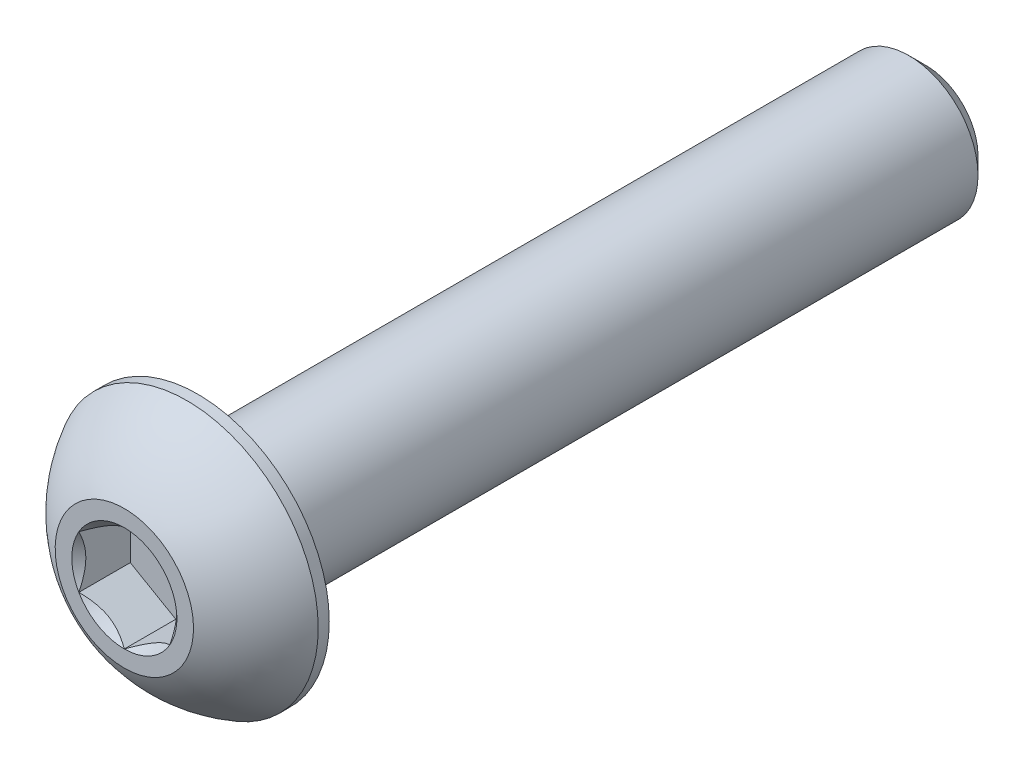
SolidWorks part; units mm, degrees
material "Alloy Steel"
ref_plane "Front" through (0, 0, 0) normal (0, 0, 1) x (1, 0, 0)
ref_plane "Top" through (0, 0, 0) normal (0, 1, 0) x (1, 0, 0)
ref_plane "Right" through (0, 0, 0) normal (1, 0, 0) x (0, 0, -1)
sketch "Sketch1" plane through (0, 0, 0) normal (1, 0, 0) x (0, 0, -1)
  line L2 (2.5654, 2.413) -> (27.9654, 2.413)
  line L3 (27.9654, 2.413) -> (27.9654, 0)
  line L4 (27.9654, 0) -> (2.5654, 0)
  line L6 (2.1806, 4.5847) -> (2.5654, 4.5847) construction
  line L7 (27.9654, 2.413) -> (27.9654, -2.413) construction
  line L8 (0, 0) -> (2.5654, 0) construction
  line L9 (2.5654, 4.5847) -> (2.5654, -4.5847) construction
  line L11 (2.5654, 2.413) -> (2.5654, 0)
  line L13 (0, 1.5875) -> (0, -1.5875) construction
  line L14 (0, 1.5875) -> (0, 2.413) construction
  arc A3 (0, 2.413) -> (2.1806, 4.5847) centre (4.5749, 0) cw construction
  dimension "D1" = 0.3848
revolve "Revolve1" add sketch "Sketch1" angle 360 mid plane about L4
sketch "Sketch3" plane through (0, 0, -27.9654) normal (0, 0, -1) x (-1, 0, 0)
  circle A0 centre (0, 0) radius 2.413
curve "Helix/Spiral1" pitch 0.7937 height 26.1937 turns 33
sketch "Sketch2" plane through (0, 0, 0) normal (1, 0, 0) x (0, 0, -1)
  line L0 (27.9654, 2.413) -> (28.6599, 2.413)
  line L1 (28.6599, 2.413) -> (28.3623, 1.8974)
  line L2 (28.3623, 1.8974) -> (28.2631, 1.8974)
  line L3 (28.2631, 1.8974) -> (27.9654, 2.413)
  line L4 (28.1142, 2.1552) -> (28.5111, 2.1552) construction
  dimension "D1" = 60
  dimension "D2" = 0.0992
  dimension "D3" = 0.3969
chamfer "Chamfer1" distance 0.5953 angle 45 1 edges at (0, 2.413, -27.9654)
sweep "Cut-Sweep1" [suppressed] cut profiles "Sketch2" path "Helix/Spiral1"
sketch "Sketch7" plane through (0, 0, 0) normal (1, 0, 0) x (0, 0, -1)
  line L6 (2.1806, 4.5847) -> (2.5654, 4.5847) construction
  line L8 (0, 0) -> (2.5654, 0) construction
  line L11 (2.5654, 4.5847) -> (2.5654, -4.5847) construction
  line L12 (2.1806, 4.5847) -> (2.5654, 4.5847)
  line L13 (0, 0) -> (2.5654, 0)
  line L14 (0, 1.5875) -> (0, -1.5875) construction
  line L15 (2.5654, 4.5847) -> (2.5654, 0)
  line L16 (0, 2.413) -> (0, 0)
  arc A2 (2.1806, 4.5847) -> (0, 2.413) centre (4.5749, 0) ccw construction
  arc A3 (2.1806, 4.5847) -> (0, 2.413) centre (4.5749, 0) ccw
revolve "Revolve2" add sketch "Sketch7" angle 360 mid plane about L13
sketch "Sketch5" plane through (0, 0, 0) normal (0, 0, 1) x (1, 0, 0)
  line L1 (1.5875, -0.9165) -> (1.5875, 0.9165)
  line L2 (1.5875, 0.9165) -> (0, 1.8331)
  line L3 (0, 1.8331) -> (-1.5875, 0.9165)
  line L4 (-1.5875, 0.9165) -> (-1.5875, -0.9165)
  line L5 (-1.5875, -0.9165) -> (0, -1.8331)
  line L6 (0, -1.8331) -> (1.5875, -0.9165)
  circle A0 centre (0, 0) radius 1.5875 construction
extrude "Cut-Extrude2" cut sketch "Sketch5" against normal blind 1.7958
sketch "Sketch6" plane through (0, 0, 0) normal (0, 0, 1) x (1, 0, 0)
  circle A0 centre (0, 0) radius 1.8331
extrude "Cut-Extrude3" cut sketch "Sketch6" against normal blind 1.7958 draft 45
sketch "Sketch9" [suppressed] plane through (0, 0, -2.2098) normal (0, 0, 1) x (1, 0, 0)
  circle A2 centre (0, 0) radius 2.0828
extrude "Boss-Extrude2" [suppressed] add sketch "Sketch9" against normal offset from surface (3.175 mm away) 22.225 up to face at (0, 1.8177, -27.9654)
sketch "Sketch10" plane through (0, 0, 0) normal (1, 0, 0) x (0, 0, -1)
  line L0 (27.9654, 2.413) -> (27.9654, -2.413) construction
  point P0 (26.7748, -2.413)
  dimension "D1" = 1.1906
equation "\"D3@Helix/Spiral1\" = \"Lg@Sketch1\" + \"D4@Helix/Spiral1\""
equation "\"D2@Sketch2\" = \"D4@Helix/Spiral1\" * .125"
equation "\"D3@Sketch2\" = \"D4@Helix/Spiral1\" * .5"
equation "\"D1@Chamfer1\" = \"D4@Helix/Spiral1\" * .75"
equation "\"D1@Cut-Extrude2\" = \"Head Ht@Sketch1\" * .7"
equation "\"D1@Sketch1\" = \"Head Ht@Sketch1\" * .15"
equation "\"D1@Sketch10\" = \"D4@Helix/Spiral1\" * 1.5"
equation "\"D1@Cut-Extrude3\" = \"D1@Cut-Extrude2\""
